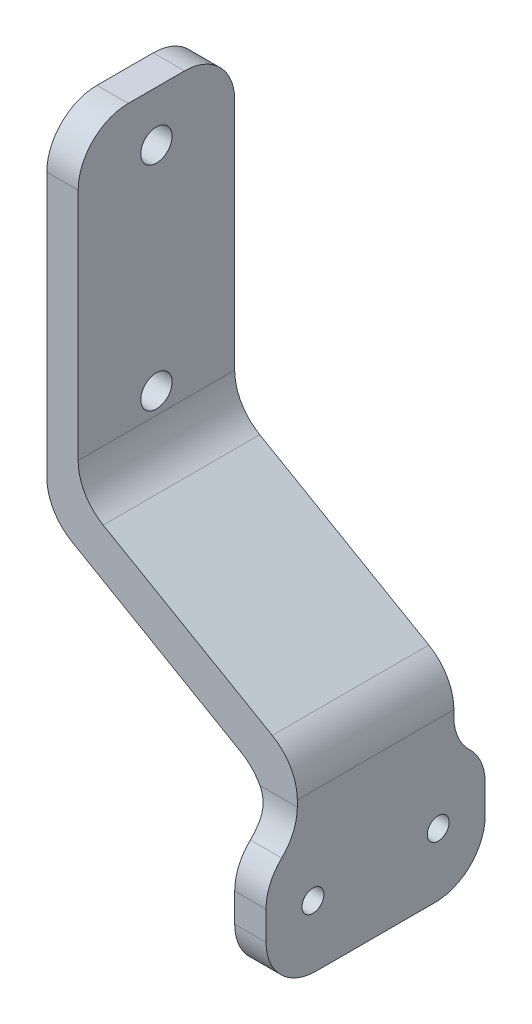
SolidWorks part; units mm, degrees
ref_plane "Front Plane" through (0, 0, 0) normal (0, 0, 1) x (1, 0, 0)
ref_plane "Top Plane" through (0, 0, 0) normal (0, 1, 0) x (1, 0, 0)
ref_plane "Right Plane" through (0, 0, 0) normal (1, 0, 0) x (0, 0, -1)
sketch "Sketch1" plane through (0, 0, 0) normal (0, 0, 1) x (1, 0, 0)
  line L0 (0, 0) -> (0, 25)
  line L1 (0, 25) -> (30, 25)
  line L2 (30, 25) -> (30, 0)
  line L3 (30, 0) -> (0, 0)
  dimension "D1" = 30
  dimension "D2" = 25
extrude "Boss-Extrude1" add sketch "Sketch1" along normal mid plane 25
sketch "Sketch2" plane through (30, 0, 0) normal (1, 0, 0) x (0, 0, -1)
  line L1 (-17.5, -25) -> (17.5, -25)
  line L2 (-17.5, -25) -> (-17.5, -5)
  line L3 (-17.5, -5) -> (17.5, -5)
  line L4 (17.5, -25) -> (17.5, -5)
  line L5 (-17.5, -25) -> (17.5, -5) construction
  line L6 (-17.5, -5) -> (17.5, -25) construction
  line L7 (12.5, 0) -> (12.5, 25) construction
  line L8 (-12.5, 25) -> (12.5, 25) construction
  line L9 (-12.5, 0) -> (12.5, 0) construction
  line L11 (-12.5, 25) -> (12.5, 25)
  line L12 (-12.5, 25) -> (-12.5, -5)
  line L13 (-12.5, -5) -> (12.5, -5)
  line L14 (12.5, 25) -> (12.5, -5)
  point P0 (0, -15)
  point P10 (0, 25)
  line M5 (12.5, 0) -> (12.5, 25)
  line M6 (12.5, 25) -> (-12.5, 25)
  line M7 (-12.5, 25) -> (-12.5, 0)
  line M8 (-12.5, 0) -> (12.5, 0)
  dimension "D1" = 35
  dimension "D2" = 20
  dimension "D3" = 5
extrude "Boss-Extrude2" add sketch "Sketch2" along normal blind 5 contours M8 M5 M6 M7 | L14 L12 L3 M8 | L1 L4 L3 L2 region at (30, -15, 0) region at (30, -2.5, 0) region at (30, 12.5, 0)
sketch "Sketch5" plane through (0, 0, 0) normal (-1, 0, 0) x (0, 0, 1)
  line L0 (12.5, 25) -> (12.5, 0) construction
  line L1 (-12.5, 0) -> (12.5, 0)
  line L2 (-12.5, 0) -> (-12.5, 75)
  line L3 (-12.5, 75) -> (12.5, 75)
  line L4 (12.5, 0) -> (12.5, 75)
  dimension "D1" = 75
extrude "Boss-Extrude4" add sketch "Sketch5" along normal blind 5 contours L2 L1 L4 L3
sketch "Sketch6" plane through (35, 0, 0) normal (1, 0, 0) x (0, 0, -1)
  line L0 (-10, -15) -> (10, -15) construction
  line L1 (-17.5, -25) -> (-17.5, -5) construction
  circle A0 centre (-10, -15) radius 1.75
  circle A1 centre (10, -15) radius 1.75
  point P4 (0, -15)
  point P8 (-17.5, -15)
  dimension "D1" = 3.5
  dimension "D2" = 20
extrude "Cut-Extrude1" cut sketch "Sketch6" against normal through all
sketch "Sketch7" plane through (0, 0, 0) normal (1, 0, 0) x (0, 0, -1)
  line L0 (12.5, 75) -> (-12.5, 75) construction
  line L1 (12.5, 25) -> (-12.5, 25) construction
  circle A0 centre (0, 67) radius 2.5
  circle A1 centre (0, 33) radius 2.5
  point P7 (0, 75)
  dimension "D1" = 5
  dimension "D2" = 8
  dimension "D3" = 8
extrude "Cut-Extrude2" cut sketch "Sketch7" against normal through all
chamfer "Chamfer1" distance 35 angle 30 2 edges at (-5, 0, 0) (35, 25, 0) first distance on face at (12.5, 0, 0) first distance on face at (17.5, 25, 0)
fillet "Fillet1" radius 8 10 edges at (32.5, -25, 17.5) (32.5, -5, 17.5) (32.5, -25, -17.5) (32.5, -5, -17.5) (30, 0, 0) (35, 4.7927, 0) (-5, 20.2073, 0) (0, 25, 0) (-2.5, 75, 12.5) (-2.5, 75, -12.5)
fillet "Fillet2" radius 8 2 edges at (32.5, -5, -12.5) (32.5, -5, 12.5)
